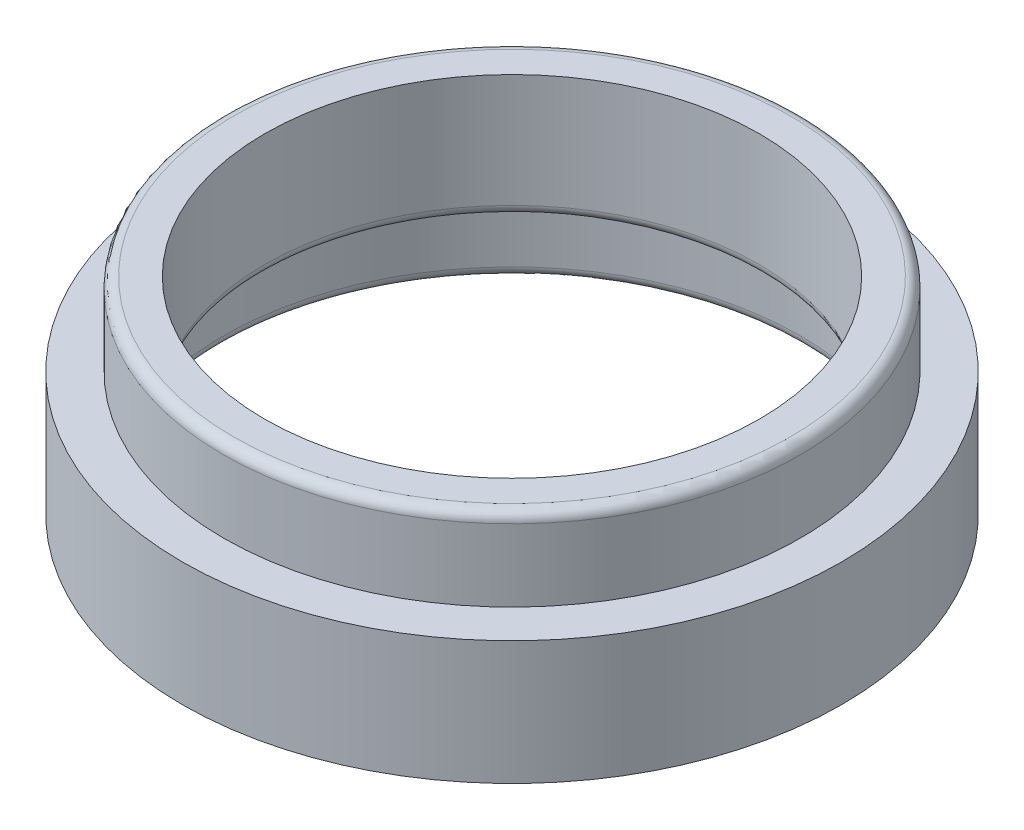
SolidWorks part; units mm, degrees
material "PLA Black"
ref_plane "Front Plane" through (0, 0, 0) normal (0, 0, 1) x (1, 0, 0)
ref_plane "Top Plane" through (0, 0, 0) normal (0, 1, 0) x (1, 0, 0)
ref_plane "Right Plane" through (0, 0, 0) normal (1, 0, 0) x (0, 0, -1)
sketch "Sketch1" plane through (0, 0, 0) normal (1, 0, 0) x (0, 0, -1)
  line L0 (0, -32.3252) -> (0, 32.3252) construction
  line L1 (22.225, 11.1125) -> (22.225, 4.7625)
  line L2 (22.225, 4.7625) -> (25.4, 4.7625)
  line L3 (25.4, 4.7625) -> (25.4, -4.7625)
  line L4 (25.4, -4.7625) -> (22.225, -4.7625)
  line L5 (22.225, -4.7625) -> (22.225, 1.5875)
  line L6 (22.225, 1.5875) -> (19.05, 1.5875)
  line L8 (19.05, 11.1125) -> (22.225, 11.1125)
  line L13 (19.05, 1.5875) -> (19.05, 11.1125)
  point P4 (0, 0)
  point P8 (0, 0)
  point P12 (25.4, 0)
  point P15 (48.1096, 40.226)
  dimension "D1" = 3.175
  dimension "D2" = 3.175
  dimension "D3" = 6.35
  dimension "D4" = 50.8
revolve "Revolve1" add sketch "Sketch1" angle 360 about L0
fillet "Fillet1" radius 0.7937 4 edges at (0, 1.5875, -22.225) (0, -4.7625, -22.225) (0, 11.1125, -22.225) (0, 1.5875, -19.05)
